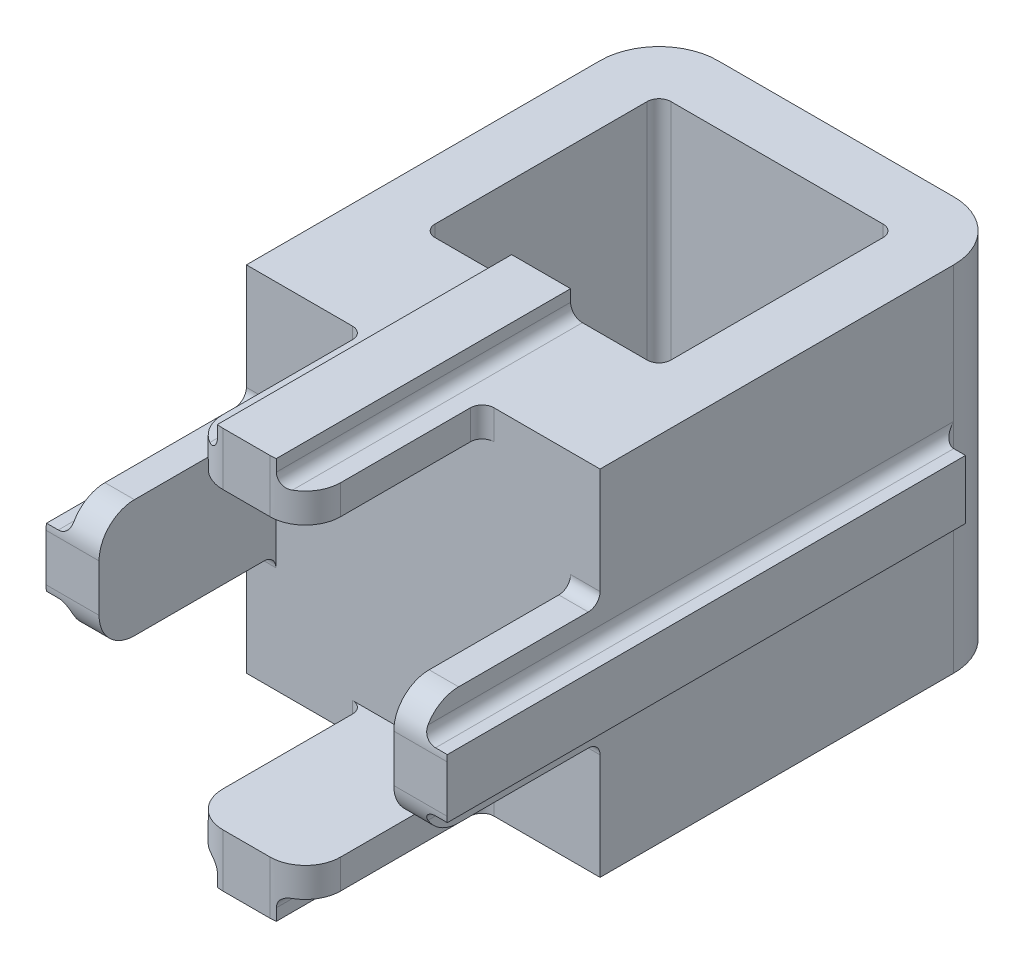
SolidWorks part; units mm, degrees
ref_plane "Plan de face" through (0, 0, 0) normal (0, 0, 1) x (1, 0, 0)
ref_plane "Plan de dessus" through (0, 0, 0) normal (0, 1, 0) x (1, 0, 0)
ref_plane "Plan de droite" through (0, 0, 0) normal (1, 0, 0) x (0, 0, -1)
sketch "Sketch1" plane through (0, 0, 0) normal (0, 0, 1) x (1, 0, 0)
  line L1 (15, -15) -> (-15, -15)
  line L2 (15, -15) -> (15, 15)
  line L3 (15, 15) -> (-15, 15)
  line L4 (-15, -15) -> (-15, 15)
  line L5 (15, -15) -> (-15, 15) construction
  line L6 (15, 15) -> (-15, -15) construction
  point P0 (0, 0)
  dimension "D1" = 30
  dimension "D2" = 30
extrude "Boss-Extrude1" add sketch "Sketch1" along normal blind 35
sketch "Sketch2" plane through (0, 15, 0) normal (0, 1, 0) x (1, 0, 0)
  line L0 (15, 0) -> (-15, 0) construction
  line L1 (10, -25) -> (-10, -25)
  line L2 (10, -25) -> (10, -5)
  line L3 (10, -5) -> (-10, -5)
  line L4 (-10, -25) -> (-10, -5)
  line L5 (10, -25) -> (-10, -5) construction
  line L6 (10, -5) -> (-10, -25) construction
  line L7 (15, -35) -> (15, 0) construction
  point P0 (0, -15)
  dimension "D1" = 5
  dimension "D2" = 5
  dimension "D3" = 20
  dimension "D4" = 20
extrude "Cut-Extrude1" cut sketch "Sketch2" against normal offset from surface (20 mm away) 10 up to face at (0, -15, 17.5)
sketch "Sketch3" plane through (0, 0, 35) normal (0, 0, 1) x (1, 0, 0)
  line L0 (15, 15) -> (-15, 15) construction
  line L1 (-5, 15) -> (5, 15)
  line L2 (-5, 15) -> (-5, 12.5)
  line L3 (-5, 12.5) -> (5, 12.5)
  line L4 (5, 15) -> (5, 12.5)
  line L5 (-15, 15) -> (-15, -15) construction
  line L6 (15, 5) -> (12.5, 5)
  line L7 (15, 5) -> (15, -5)
  line L8 (15, -5) -> (12.5, -5)
  line L9 (12.5, 5) -> (12.5, -5)
  line L10 (5, -15) -> (5, -12.5)
  line L11 (5, -15) -> (-5, -15)
  line L12 (-5, -15) -> (-5, -12.5)
  line L13 (5, -12.5) -> (-5, -12.5)
  line L14 (-15, -5) -> (-12.5, -5)
  line L15 (-15, -5) -> (-15, 5)
  line L16 (-15, 5) -> (-12.5, 5)
  line L17 (-12.5, -5) -> (-12.5, 5)
  dimension "D1" = 10
  dimension "D2" = 10
  dimension "D3" = 2.5
  dimension "D4" = 4
extrude "Boss-Extrude2" add sketch "Sketch3" along normal blind 15
fillet "Fillet3" radius 5 2 edges at (-15, 0, 0) (15, 0, 0)
sketch "Sketch4" plane through (15, 0, 0) normal (1, 0, 0) x (0, 0, -1)
  line L0 (-50, -5) -> (-50, 5) construction
  line L1 (-50, -2.5) -> (-6, -2.5)
  line L2 (-50, -2.5) -> (-50, 2.5)
  line L3 (-50, 2.5) -> (-6, 2.5)
  line L4 (-6, -2.5) -> (-6, 2.5)
  line L5 (-50, 5) -> (-35, 5) construction
  line L7 (-5, -15) -> (-5, 15) construction
  point P8 (-50, -2.5)
  dimension "D1" = 5
  dimension "D2" = 2.5
  dimension "D3" = 1
extrude "Boss-Extrude3" add sketch "Sketch4" along normal blind 2
pattern_circular "CirPattern1" count 3 every 90 about axis through (0, 0, 0) along (0, 0, -1) of "Boss-Extrude3"
sketch "Sketch5" plane through (0, 15, 0) normal (0, 1, 0) x (1, 0, 0)
  line L0 (5, -50) -> (-5, -50) construction
  line L1 (-2.5, -50) -> (2.5, -50)
  line L2 (-2.5, -50) -> (-2.5, -25)
  line L3 (-2.5, -25) -> (2.5, -25)
  line L4 (2.5, -50) -> (2.5, -25)
  line L5 (-10, -25) -> (10, -25) construction
  line L6 (5, -50) -> (5, -35) construction
  dimension "D1" = 5
  dimension "D2" = 2.5
extrude "Boss-Extrude4" add sketch "Sketch5" along normal blind 2
fillet "Fillet1" radius 1 23 edges at (13.75, 5, 35) (5, 13.75, 35) (-5, 13.75, 35) (-13.75, 5, 35) (-13.75, -5, 35) (-5, -13.75, 35) (13.75, -5, 35) (5, -13.75, 35) (-2.5, 15, 37.5) (2.5, 15, 37.5) (15, 2.5, 28) (15, -2.5, 28) (2.5, -15, 28) (-2.5, -15, 28) (-15, -2.5, 28) (-15, 2.5, 28) (-10, 5, 25) (10, 5, 25) (-10, 5, 5) (10, 5, 5) (-15, 0, 6) (0, -15, 6) (15, 0, 6)
fillet "Fillet2" radius 3 8 edges at (-13.75, 5, 50) (-13.75, -5, 50) (5, -13.75, 50) (-5, -13.75, 50) (13.75, -5, 50) (13.75, 5, 50) (5, 13.75, 50) (-5, 13.75, 50)
